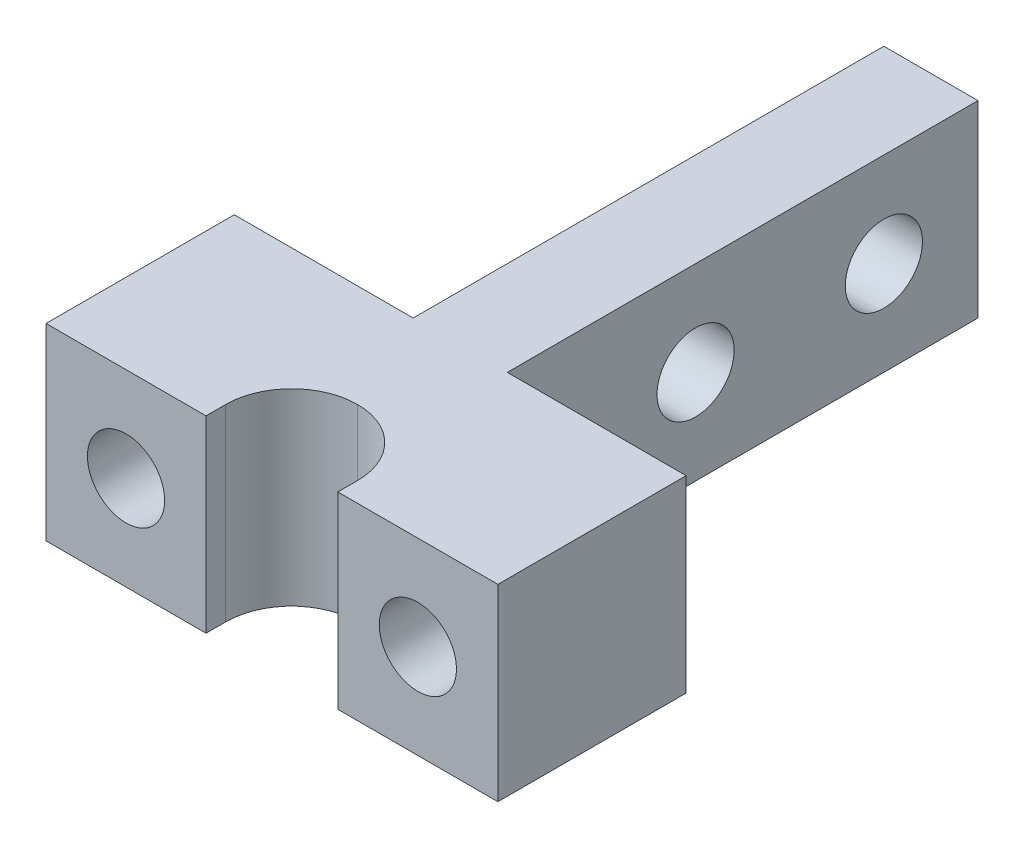
SolidWorks part; units mm, degrees
ref_plane "Спереди" through (0, 0, 0) normal (0, 0, 1) x (1, 0, 0)
ref_plane "Сверху" through (0, 0, 0) normal (0, 1, 0) x (1, 0, 0)
ref_plane "Справа" through (0, 0, 0) normal (1, 0, 0) x (0, 0, -1)
sketch "Sketch1" plane through (0, 0, 0) normal (0, 1, 0) x (1, 0, 0)
  line L0 (-22.986, 8.6014) -> (-22.986, -11.3986)
  line L1 (-22.986, -11.3986) -> (-5.986, -11.3986)
  line L2 (-5.986, -11.3986) -> (-5.986, -2.3077)
  line L3 (-5.986, -2.3077) -> (8.014, -2.3077)
  line L4 (8.014, -2.3077) -> (8.014, -11.3986)
  line L5 (8.014, -11.3986) -> (25.014, -11.3986)
  line L6 (25.014, -11.3986) -> (25.014, 8.6014)
  line L7 (25.014, 8.6014) -> (6.014, 8.6014)
  line L8 (6.014, 8.6014) -> (6.014, 58.6014)
  line L9 (6.014, 58.6014) -> (-3.986, 58.6014)
  line L10 (-3.986, 58.6014) -> (-3.986, 8.6014)
  line L11 (-3.986, 8.6014) -> (-22.986, 8.6014)
  dimension "D1" = 20
  dimension "D2" = 48
  dimension "D3" = 50
  dimension "D4" = 10
  dimension "D5" = 14
extrude "Boss-Extrude1" add sketch "Sketch1" along normal blind 20
sketch "Sketch3" plane through (0, 0, 11.3986) normal (0, 0, 1) x (1, 0, 0)
  line L0 (-22.986, 10) -> (-5.986, 10) construction
  line L1 (-22.986, 20) -> (-22.986, 0) construction
  line L2 (-5.986, 20) -> (-5.986, 0) construction
  line L4 (8.014, 10) -> (25.014, 10) construction
  line L5 (8.014, 20) -> (8.014, 0) construction
  line L6 (25.014, 20) -> (25.014, 0) construction
  circle A0 centre (-14.486, 10) radius 4.1
  circle A1 centre (16.514, 10) radius 4.1
  dimension "D1" = 8.2
extrude "Cut-Extrude1" cut sketch "Sketch3" against normal through all
sketch "Sketch4" plane through (6.014, 0, 0) normal (1, 0, 0) x (0, 0, -1)
  line L0 (58.6014, 10) -> (8.6014, 10) construction
  line L1 (58.6014, 20) -> (58.6014, 0) construction
  line L2 (8.6014, 20) -> (8.6014, 0) construction
  circle A0 centre (28.6014, 10) radius 4.1
  circle A1 centre (48.6014, 10) radius 4.1
  dimension "D1" = 8.2
  dimension "D2" = 20
  dimension "D3" = 20
extrude "Cut-Extrude2" cut sketch "Sketch4" against normal through all
fillet "Fillet1" radius 7 2 edges at (-5.986, 10, 2.3077) (8.014, 10, 2.3077)
